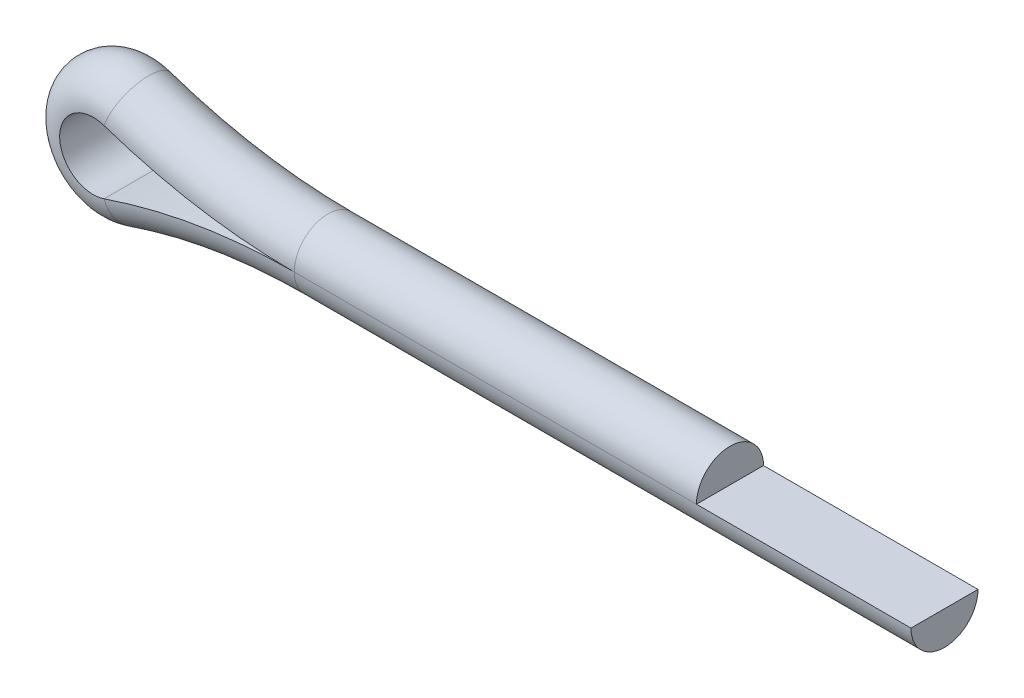
SolidWorks part; units mm, degrees
ref_plane "Front" through (0, 0, 0) normal (0, 0, 1) x (1, 0, 0)
ref_plane "Top" through (0, 0, 0) normal (0, 1, 0) x (1, 0, 0)
ref_plane "Right" through (0, 0, 0) normal (1, 0, 0) x (0, 0, -1)
ref_plane "Plane1" through (5, 0, 0) normal (1, 0, 0) x (0, 0, -1)
sketch "PathSke" plane through (1.208, 1.808, 0) normal (0, 0, 1) x (0, 1, 0)
  line L0 (-1.558, -3.792) -> (-1.558, -0.792)
  line L1 (-2.058, -0.792) -> (-2.058, -5.392)
  line L2 (-1.808, 1.208) -> (-1.808, -5.7761) construction
  arc A0 (-2.058, -0.792) -> (-2.2809, 0.5458) centre (-6.183, -0.792) ccw
  arc A1 (-1.558, -0.792) -> (-1.335, 0.5458) centre (2.567, -0.792) cw
  arc A3 (-1.335, 0.5458) -> (-2.2809, 0.5458) centre (-1.808, 0.708) ccw
sketch "SectionSke" plane through (5, 0.15, 0.15) normal (1, 0, 0) x (0, 1, 0)
  line L0 (-0.15, -0.4) -> (-0.15, 0.1)
  arc A0 (-0.15, -0.4) -> (-0.15, 0.1) centre (-0.15, -0.15) ccw
sweep "Body" add profiles "SectionSke" path "PathSke"
equation "\"d/2@PathSke\" = \"d@PathSke\" / 2"
equation "\"R@SectionSke\" = \"d@PathSke\" / 2"
equation "\"d1@SectionSke\" = \"d@PathSke\""
equation "\"D1@Plane1\" = \"b@PathSke\" + \"l@PathSke\""
